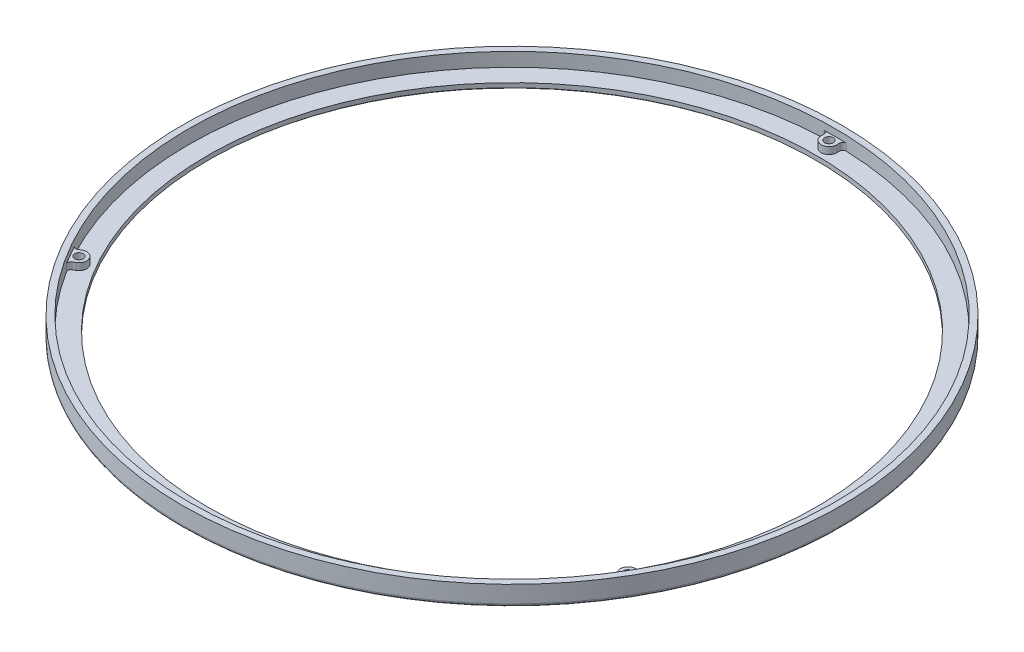
SolidWorks part; units mm, degrees
ref_plane "前视基准面" through (0, 0, 0) normal (0, 0, 1) x (1, 0, 0)
ref_plane "上视基准面" through (0, 0, 0) normal (0, 1, 0) x (1, 0, 0)
ref_plane "右视基准面" through (0, 0, 0) normal (1, 0, 0) x (0, 0, -1)
other "Configuration Table"
sketch "草图1" plane through (0, 0, 0) normal (0, 1, 0) x (1, 0, 0)
  circle A0 centre (0, 0) radius 52.5
  circle A1 centre (0, 0) radius 48.5
  dimension "D1" = 105
  dimension "D2" = 97
extrude "凸台-拉伸1" add sketch "草图1" along normal blind 3.2 contours A0 | A1
sketch "草图2" plane through (0, 3.2, 0) normal (0, 1, 0) x (1, 0, 0)
  circle A0 centre (0, 0) radius 51.5
  dimension "D1" = 103
extrude "切除-拉伸1" cut sketch "草图2" against normal blind 2.2
sketch "草图3" plane through (0, 1, 0) normal (0, 1, 0) x (1, 0, 0)
  line L0 (0, 0) -> (0, 50.5) construction
  line L1 (0, 0) -> (43.7343, -25.25) construction
  line L2 (0, 0) -> (-43.7343, -25.25) construction
  circle A0 centre (0, 0) radius 50.5 construction
  circle A1 centre (-43.7343, -25.25) radius 1.25
  circle A2 centre (43.7343, -25.25) radius 1.25
  circle A3 centre (0, 50.5) radius 1.25
  dimension "D1" = 101
  dimension "D4" = 2.5
  dimension "D5" = 2.5
  dimension "D6" = 2.5
  dimension "D2" = 120
  dimension "D3" = 120
extrude "凸台-拉伸2" add sketch "草图3" along normal blind 1.1
sketch "草图4" plane through (0, 1, 0) normal (0, 1, 0) x (1, 0, 0)
  line L0 (-44.3593, -24.1675) -> (-45.2253, -24.6675)
  line L1 (-1.25, 51.5) -> (1.25, 51.5)
  line L2 (-1.25, 51.5) -> (-1.25, 50.5)
  line L3 (-1.25, 50.5) -> (1.25, 50.5)
  line L4 (1.25, 51.5) -> (1.25, 50.5)
  line L5 (-1.25, 51.5) -> (1.25, 50.5) construction
  line L6 (-1.25, 50.5) -> (1.25, 51.5) construction
  line L11 (-45.2253, -24.6675) -> (-43.9753, -26.8325)
  line L12 (-43.9753, -26.8325) -> (-43.1093, -26.3325)
  line L13 (-43.1093, -26.3325) -> (-44.3593, -24.1675)
  line L14 (44.3593, -24.1675) -> (45.2253, -24.6675)
  line L15 (45.2253, -24.6675) -> (43.9753, -26.8325)
  line L16 (43.9753, -26.8325) -> (43.1093, -26.3325)
  line L17 (43.1093, -26.3325) -> (44.3593, -24.1675)
  arc A1 (0.7574, 51.4944) -> (-0.7574, 51.4944) centre (0, 0) ccw
  arc A3 (-44.9742, -25.0913) -> (-44.2168, -26.4031) centre (0, 0) ccw
  arc A7 (44.2168, -26.4031) -> (44.9742, -25.0913) centre (0, 0) ccw
  arc A14 (0.7574, 51.4944) -> (-0.7574, 51.4944) centre (0, 0) ccw
  arc A15 (-0.7574, 51.4944) -> (0.7574, 51.4944) centre (0, 50.5) ccw
  arc A16 (-0.7574, 51.4944) -> (0.7574, 51.4944) centre (0, 50.5) ccw
  arc A17 (-44.9742, -25.0913) -> (-44.2168, -26.4031) centre (0, 0) ccw
  arc A18 (-44.2168, -26.4031) -> (-44.9742, -25.0913) centre (-43.7343, -25.25) ccw
  arc A19 (-44.2168, -26.4031) -> (-44.9742, -25.0913) centre (-43.7343, -25.25) ccw
  arc A20 (44.2168, -26.4031) -> (44.9742, -25.0913) centre (0, 0) ccw
  arc A21 (44.9742, -25.0913) -> (44.2168, -26.4031) centre (43.7343, -25.25) ccw
  arc A22 (44.9742, -25.0913) -> (44.2168, -26.4031) centre (43.7343, -25.25) ccw
  point P0 (0, 51)
  dimension "D2" = 2.5
  dimension "D3" = 1
  dimension "D4" = 30
  dimension "D5" = 1
  dimension "D7" = 2.5
  dimension "D8" = 30
  dimension "D9" = 1
  dimension "D10" = 2.5
  dimension "D1" = 0
  dimension "D6" = 0
  dimension "D11" = 0
extrude "凸台-拉伸3" add sketch "草图4" along normal blind 1.1 contours A22 A20 L15 L14 | L17 L14 L15 L16 | L2 L1 L4 L3 | L13 L0 L11 L12 region at (44.9463, 1, 24.6772)
sketch "草图5" plane through (0, 3.2, 0) normal (0, 1, 0) x (1, 0, 0)
  circle A0 centre (0, 0) radius 50.5 construction
  circle A1 centre (0, 50.5) radius 0.7
  circle A2 centre (-43.7343, -25.25) radius 0.7
  circle A3 centre (43.7343, -25.25) radius 0.7
  dimension "D1" = 101
  dimension "D2" = 1.4
  dimension "D3" = 1.4
  dimension "D4" = 1.4
extrude "切除-拉伸2" cut sketch "草图5" against normal through all
sketch "草图6" plane through (0, 0, 0) normal (0, -1, 0) x (1, 0, 0)
  circle A0 centre (-43.7343, 25.25) radius 1.5
  circle A1 centre (0, -50.5) radius 1.5
  circle A2 centre (43.7343, 25.25) radius 1.5
  dimension "D1" = 3
extrude "切除-拉伸3" cut sketch "草图6" against normal blind 0.7
fillet "圆角1" radius 0.5 7 edges at (45.2122, 1.55, 24.6599) (43.9622, 1.55, 26.8249) (-45.2122, 1.55, 24.6599) (-43.9622, 1.55, 26.8249) (-1.25, 1.55, -51.4848) (1.25, 1.55, -51.4848) (0, 0, 52.5)
chamfer "倒角1" distance 0.3 angle 50 1 edges at (0, 0, 48.5) first distance on face at (0, 0, 48.5)
